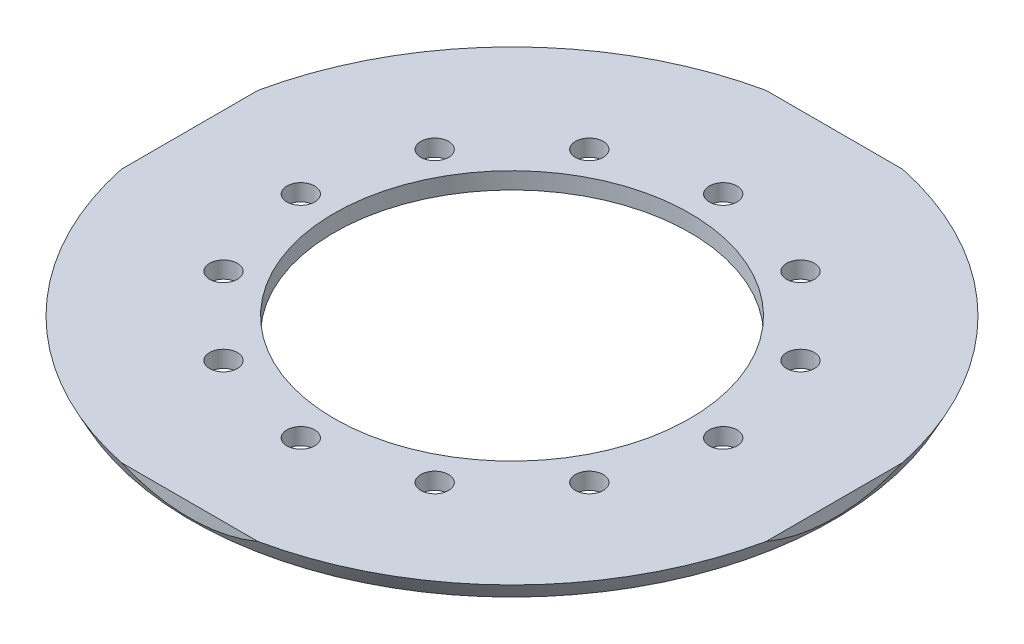
SolidWorks part; units mm, degrees
ref_plane "Front Plane" through (0, 0, 0) normal (0, 0, 1) x (1, 0, 0)
ref_plane "Top Plane" through (0, 0, 0) normal (0, 1, 0) x (1, 0, 0)
ref_plane "Right Plane" through (0, 0, 0) normal (1, 0, 0) x (0, 0, -1)
sketch "Main Revolve Sketch" plane through (0, 0, 0) normal (0, 0, 1) x (1, 0, 0)
  line L0 (0, 0) -> (0, 96.25) construction
  line L3 (-82.5, 13.75) -> (-82.5, 0) construction
  line L4 (-82.5, 0) -> (-82.5, -13.75) construction
  line L8 (0, 96.25) -> (96.25, 96.25) construction
  line L9 (0, -96.25) -> (96.25, -96.25) construction
  line L11 (0, 0) -> (0, -96.25) construction
  line L13 (0, 0) -> (0, -50) construction
  line L14 (0, -50) -> (-74.1093, -50)
  line L16 (0, -53.75) -> (-72.1543, -53.75)
  line L17 (0, -50) -> (0, -53.75)
  arc A0 (0, 96.25) -> (-82.5, 13.75) centre (0, 13.75) ccw construction
  arc A1 (-74.1093, -50) -> (-72.1543, -53.75) centre (0, -13.75) ccw
  dimension "D1" = 82.5
  dimension "D2" = 27.5
  dimension "D3" = 50
  dimension "D4" = 3.75
revolve "Main Revolve" add sketch "Main Revolve Sketch" angle 360 about L0
sketch "Sketch3" plane through (0, 0, 0) normal (0, 0, 1) x (1, 0, 0)
  circle A9 centre (0, 0) radius 125
  dimension "D1" = 250
extrude "Cut-Extrude2" cut sketch "Sketch3" against normal offset from surface (427.5 mm away) 72.5 from offset 500 contours A9 up to plane "Front Plane"
pattern_circular "CirPattern4" count 4 over 360 about axis through (0, -50, 0) along (0, -1, 0) of "Cut-Extrude2"
sketch "Sketch5" plane through (0, 0, 0) normal (0, 1, 0) x (1, 0, 0)
  line L8 (0, 0) -> (0, -47.5) construction
  line L9 (-23.75, 41.1362) -> (0, 47.5) construction
  line L10 (47.5, 0) -> (0, 0) construction
  line L11 (0, 0) -> (41.1362, 23.75) construction
  line L12 (41.1362, 23.75) -> (23.75, 41.1362) construction
  line L13 (23.75, 41.1362) -> (0, 0) construction
  line L14 (0, 0) -> (0, 47.5) construction
  line L15 (0, 47.5) -> (23.75, 41.1362) construction
  line L16 (-23.75, 41.1362) -> (0, 0) construction
  line L17 (0, 0) -> (-41.1362, 23.75) construction
  line L18 (-41.1362, 23.75) -> (-47.5, 0) construction
  line L19 (-47.5, 0) -> (0, 0) construction
  line L20 (0, 0) -> (-41.1362, -23.75) construction
  line L21 (47.5, 0) -> (41.1362, 23.75) construction
  line L22 (-23.75, 41.1362) -> (-41.1362, 23.75) construction
  line L23 (-41.1362, -23.75) -> (-47.5, 0) construction
  line L24 (0, 0) -> (-23.75, -41.1362) construction
  line L25 (0, 0) -> (41.1362, -23.75) construction
  line L26 (-23.75, -41.1362) -> (-41.1362, -23.75) construction
  line L29 (41.1362, -23.75) -> (47.5, 0) construction
  line L30 (-23.75, -41.1362) -> (0, -47.5) construction
  line L31 (0, -47.5) -> (23.75, -41.1362) construction
  line L32 (23.75, -41.1362) -> (41.1362, -23.75) construction
  line L33 (0, 0) -> (23.75, -41.1362) construction
  circle A8 centre (0, 0) radius 40
  circle A9 centre (0, -47.5) radius 3.125
  circle A10 centre (47.5, 0) radius 3.125
  circle A11 centre (41.1362, 23.75) radius 3.125
  circle A12 centre (23.75, 41.1362) radius 3.125
  circle A13 centre (0, 47.5) radius 3.125
  circle A14 centre (-23.75, 41.1362) radius 3.125
  circle A15 centre (-41.1362, 23.75) radius 3.125
  circle A16 centre (-47.5, 0) radius 3.125
  circle A17 centre (-41.1362, -23.75) radius 3.125
  circle A18 centre (41.1362, -23.75) radius 3.125
  circle A19 centre (-23.75, -41.1362) radius 3.125
  circle A20 centre (23.75, -41.1362) radius 3.125
  point P0 (0, 0)
  dimension "D1" = 80
  dimension "D3" = 6.25
  dimension "D2" = 47.5
extrude "Cut-Extrude3" cut sketch "Sketch5" against normal through all
